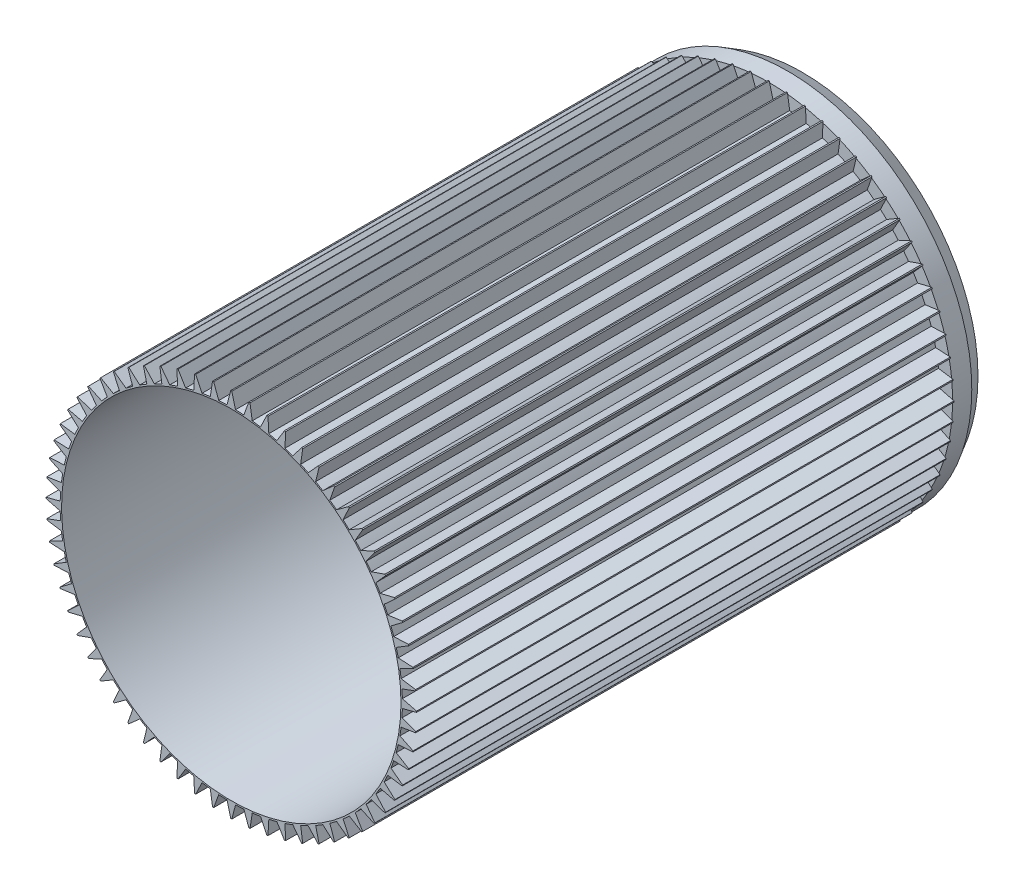
SolidWorks part; units mm, degrees
ref_plane "Front Plane" through (0, 0, 0) normal (1, 0, 0) x (0, 1, 0)
ref_plane "Top Plane" through (0, 0, 0) normal (0, 0, 1) x (0, 1, 0)
ref_plane "Right Plane" through (0, 0, 0) normal (0, 1, 0) x (-1, 0, 0)
sketch "Sketch1" plane through (0, 0, 0) normal (0, 1, 0) x (-1, 0, 0)
  line L3 (16.5, 20) -> (0, 20) construction
  line L4 (0, 20) -> (0, 0) construction
  line L5 (0, 0) -> (18, 0) construction
  line L8 (65, 0) -> (18, 0) construction
  line L9 (65, 0) -> (65, 2)
  line L10 (65, 2) -> (18, 2)
  line L13 (65, 0) -> (65, -5)
  line L14 (65, -5) -> (18, -5)
  line L15 (18, 2) -> (18, -5)
  dimension "D2" = 18
  dimension "D6" = 20
  dimension "D7" = 16.5
  dimension "D8" = 5
  dimension "D9" = 2
  dimension "D10" = 18
  dimension "D12" = 65
revolve "Revolve1" add sketch "Sketch1" angle 360 about L4
sketch "ring-1mm" plane through (0, 0, 2) normal (0, 0, 1) x (1, 0, 0)
  circle A0 centre (0, 0) radius 60
  circle A1 centre (0, 0) radius 65
  circle A2 centre (0, 0) radius 65
  dimension "D1" = 0
  dimension "D2" = 5
extrude "Boss-Extrude1" add sketch "ring-1mm" along normal blind 5
sketch "Sketch3-base-openings" plane through (0, 0, 2) normal (0, 0, 1) x (1, 0, 0)
  line L0 (0, 0) -> (60, 0) construction
  line L1 (0, 0) -> (56.3816, 20.5212) construction
  line L4 (24.3596, 8.8662) -> (54.4698, 19.8254)
  line L6 (24.3596, -8.8662) -> (54.4698, -19.8254)
  circle A0 centre (0, 0) radius 18 construction
  circle A5 centre (0, 0) radius 60 construction
  arc A29 (54.4698, 19.8254) -> (57.0557, 18.5648) centre (55.1538, 17.946) cw
  circle A30 centre (0, 0) radius 60
  arc A31 (57.0557, -18.5648) -> (57.0557, 18.5648) centre (0, 0) ccw
  arc A33 (23.1172, 6.4493) -> (24.3596, 8.8662) centre (25.0437, 6.9868) cw
  arc A35 (23.1172, -6.4493) -> (23.1172, 6.4493) centre (0, 0) ccw
  arc A36 (54.4698, -19.8254) -> (57.0557, -18.5648) centre (55.1538, -17.946) ccw
  arc A37 (23.1172, -6.4493) -> (24.3596, -8.8662) centre (25.0437, -6.9868) ccw
  point P20 (56.3816, 20.5212)
  point P26 (22.5526, 8.2085)
  point P84 (0, 0)
  dimension "D2" = 6
  dimension "D4" = 2
  dimension "D5" = 2
  dimension "D1" = 20
  dimension "D3" = 0
extrude "Cut-Extrude2" cut sketch "Sketch3-base-openings" against normal blind 240
pattern_circular "CirPattern1" count 6 over 360 about axis through (0, 0, 2) along (0, 0, 1) of "Cut-Extrude2"
chamfer "Chamfer1" distance 3 angle 60 1 edges at (65, 0, -5) first distance on face at (-40.1774, 0, -5)
sketch "Sketch2" plane through (0, 0, 7) normal (0, 0, 1) x (1, 0, 0)
  line L0 (0, 0) -> (82.0261, 0) construction
  circle A0 centre (0, 0) radius 60 construction
  circle A1 centre (0, 0) radius 60
  circle A2 centre (0, 0) radius 60.5
  dimension "D1" = 0.5
extrude "Boss-Extrude2" add sketch "Sketch2" along normal blind 190
sketch "Sketch3" plane through (0, 0, 7) normal (0, 0, 1) x (1, 0, 0)
  line L0 (0, 0) -> (100.3439, 0) construction
  line L1 (60.5, 0) -> (65.5, 0) construction
  line L2 (65.5, -0.2) -> (65.5, 0.2)
  line L3 (65.5, 0.2) -> (60.4814, 1.5)
  line L4 (60.4814, 1.5) -> (60.5, 0)
  line L5 (65.5, -0.2) -> (60.4814, -1.5)
  line L6 (60.4814, -1.5) -> (60.5, 0)
  circle A0 centre (0, 0) radius 60.5 construction
  dimension "D1" = 5
  dimension "D2" = 0.2
  dimension "D3" = 1.5
extrude "Boss-Extrude3" add sketch "Sketch3" along normal blind 190
pattern_circular "CirPattern2" count 64 over 360 about axis through (0, 0, 197) along (0, 0, 1) of "Boss-Extrude3"
